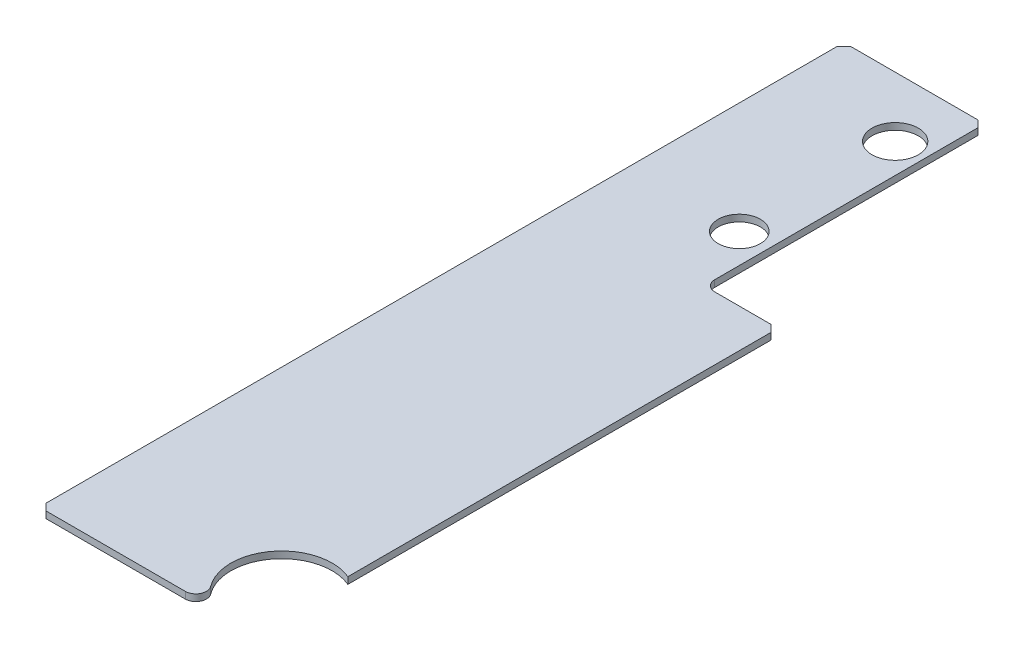
SolidWorks part; units mm, degrees
material "6061 Alloy"
ref_plane "Front" through (0, 0, 0) normal (0, 0, 1) x (1, 0, 0)
ref_plane "Top" through (0, 0, 0) normal (0, 1, 0) x (1, 0, 0)
ref_plane "Right" through (0, 0, 0) normal (1, 0, 0) x (0, 0, -1)
ref_axis "Axis1" through (0, 0, 55) along (0, 0, -1)
sketch "Sketch1" plane through (0, 0, 0) normal (0, 1, 0) x (1, 0, 0)
  line L1 (-50.8, 190.5) -> (50.8, 190.5)
  line L2 (-50.8, 190.5) -> (-50.8, -190.5)
  line L3 (-50.8, -190.5) -> (50.8, -190.5)
  line L4 (50.8, 190.5) -> (50.8, -190.5)
  line L5 (-50.8, 190.5) -> (50.8, -190.5) construction
  line L6 (-50.8, -190.5) -> (50.8, 190.5) construction
  point P0 (0, 0)
  dimension "D1" = 101.6
  dimension "D2" = 381
extrude "Boss-Extrude1" add sketch "Sketch1" along normal blind 3.175
chamfer "Chamfer1" distance 3.175 angle 45 4 edges at (-50.8, 1.5875, -190.5) (50.8, 1.5875, -190.5) (50.8, 1.5875, 190.5) (-50.8, 1.5875, 190.5)
sketch "Sketch2" plane through (0, 3.175, 0) normal (0, 1, 0) x (1, 0, 0)
  line L0 (47.625, 190.5) -> (-47.625, 190.5) construction
  line L1 (15.875, 190.5) -> (50.8, 190.5)
  line L2 (15.875, 190.5) -> (15.875, 57.6578)
  line L3 (15.875, 57.6578) -> (50.8, 57.6578)
  line L4 (50.8, 190.5) -> (50.8, 57.6578)
  line L5 (42.291, 57.6578) -> (192.659, 57.6578) construction
  line L6 (50.8, -187.325) -> (50.8, 187.325) construction
  line L7 (-50.8, 187.325) -> (-50.8, -187.325) construction
  circle A0 centre (41.5158, -168.0955) radius 23.9815
  circle A1 centre (1.8986, 162.0774) radius 10.9521
  circle A2 centre (1.8986, 88.265) radius 9.9966
  dimension "D2" = 19.9931
  dimension "D3" = 47.9629
  dimension "D4" = 21.9042
  dimension "D1" = 34.925
  dimension "D5" = 92.3158
  dimension "D6" = 355.4205
extrude "Cut-Extrude1" cut sketch "Sketch2" against normal up to next
chamfer "Chamfer2" distance 3.175 angle 45 2 edges at (50.8, 1.5875, -57.6578) (15.875, 1.5875, -190.5)
fillet "Fillet1" radius 5 1 edges at (15.875, 1.5875, -57.6578)
fillet "Fillet2" radius 5 1 edges at (32.9632, 1.5875, 190.5)
